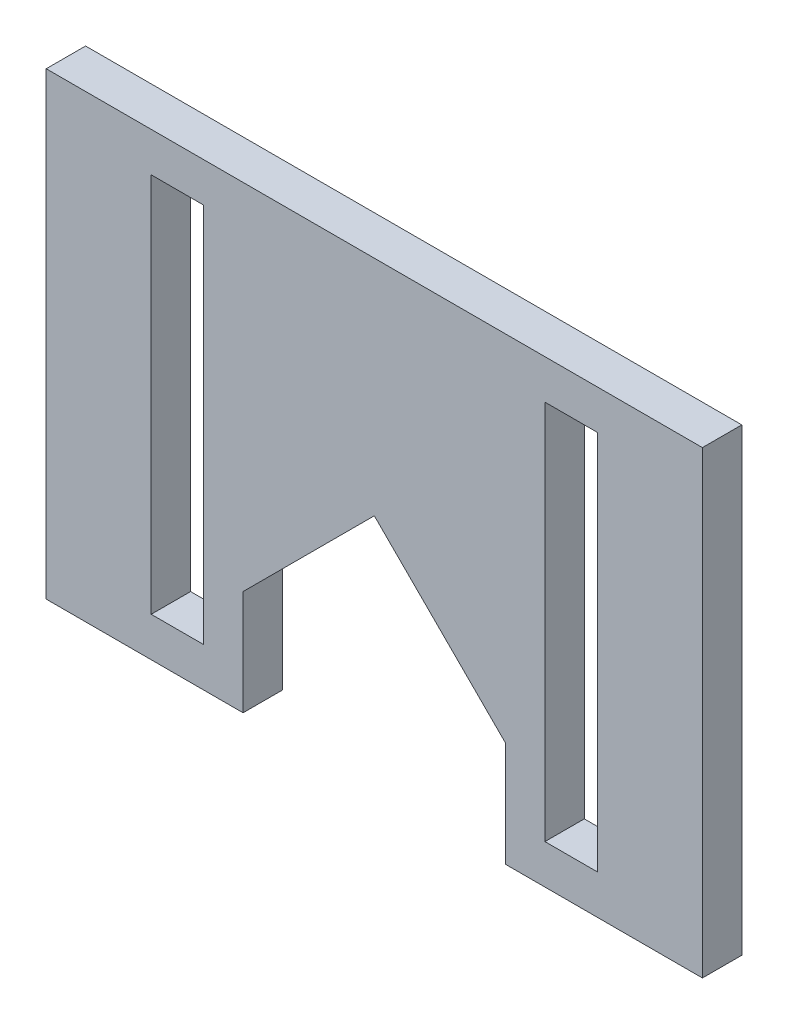
SolidWorks part; units mm, degrees
ref_plane "FRONT" through (0, 0, 0) normal (0, 0, 1) x (1, 0, 0)
ref_plane "TOP" through (0, 0, 0) normal (0, 1, 0) x (1, 0, 0)
ref_plane "RIGHT" through (0, 0, 0) normal (1, 0, 0) x (0, 0, -1)
ref_axis "X axis" through (88.99, 0, 0) along (-1, 0, 0)
ref_axis "Y axis" through (0, 55, 0) along (0, -1, 0)
ref_axis "Z axis" through (0, 0, 55) along (0, 0, -1)
sketch "Esquisse1" plane through (0, 0, 0) normal (0, 0, 1) x (1, 0, 0)
  line L0 (-35, 0) -> (-35, 8)
  line L1 (0, 0) -> (-15, 0)
  line L2 (0, 0) -> (0, 35)
  line L3 (0, 35) -> (-50, 35)
  line L4 (-50, 0) -> (-50, 35)
  line L5 (-35, 8) -> (-25, 18)
  line L6 (-25, 18) -> (-15, 8)
  line L7 (-15, 8) -> (-15, 0)
  line L8 (-12, 32) -> (-8, 32)
  line L9 (-42, 32) -> (-38, 32)
  line L10 (-42, 32) -> (-42, 3)
  line L11 (-42, 3) -> (-38, 3)
  line L12 (-38, 32) -> (-38, 3)
  line L13 (-12, 32) -> (-12, 3)
  line L14 (-12, 3) -> (-8, 3)
  line L15 (-8, 32) -> (-8, 3)
  line L16 (-35, 0) -> (-50, 0)
  dimension "D1" = 35
  dimension "D2" = 50
  dimension "D3" = 27
  dimension "D4" = 90
  dimension "D5" = 27
  dimension "D6" = 3
  dimension "D7" = 3
  dimension "D8" = 4
  dimension "D9" = 8
  dimension "D10" = 3
  dimension "D11" = 3
  dimension "D12" = 8
  dimension "D13" = 4
  dimension "D14" = 25
  dimension "D15" = 15
  dimension "D16" = 15
extrude "Boss.-Extru.2" add sketch "Esquisse1" along normal blind 3
